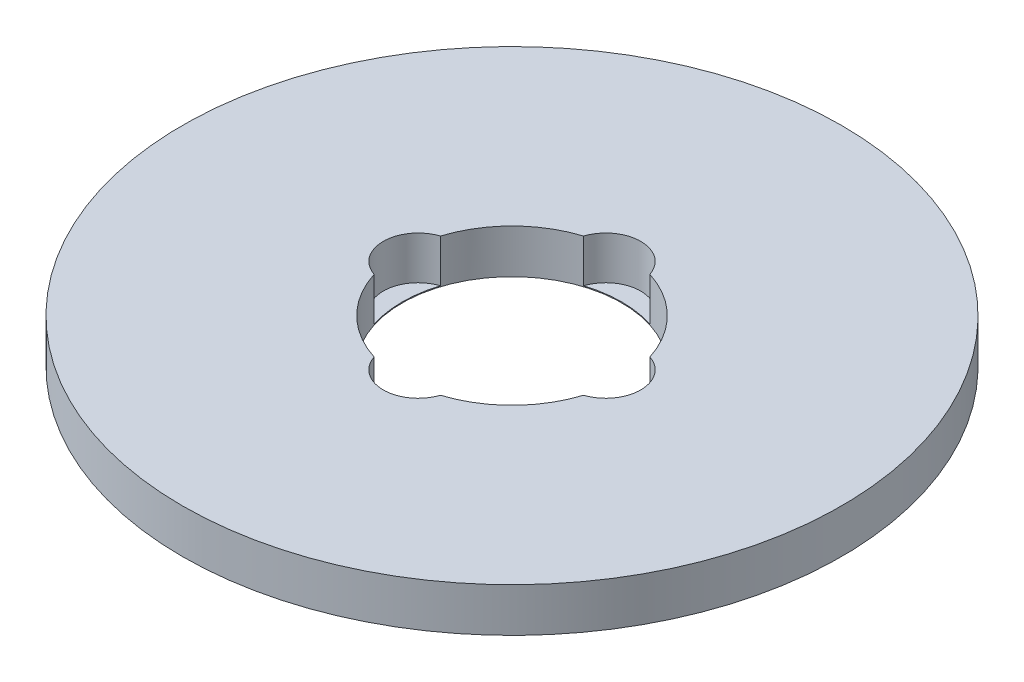
SolidWorks part; units mm, degrees
ref_plane "Front Plane" through (0, 0, 0) normal (0, 0, 1) x (1, 0, 0)
ref_plane "Top Plane" through (0, 0, 0) normal (0, 1, 0) x (1, 0, 0)
ref_plane "Right Plane" through (0, 0, 0) normal (1, 0, 0) x (0, 0, -1)
sketch "Sketch1" plane through (0, 0, 0) normal (0, 1, 0) x (1, 0, 0)
  circle A0 centre (0, 0) radius 30
  dimension "FLANGE_OD" = 60
extrude "Boss-Extrude1" add sketch "Sketch1" along normal blind 4
sketch "Sketch2" plane through (0, 0, 0) normal (0, 1, 0) x (1, 0, 0)
  circle A0 centre (0, 0) radius 10
  dimension "BORE_D" = 20
extrude "Cut-Extrude1" cut sketch "Sketch2" along normal through all
sketch "Sketch3" plane through (0, 4, 0) normal (0, 1, 0) x (1, 0, 0)
  circle A0 centre (0, 0) radius 8.5414 construction
  circle A1 centre (-8.5414, 0) radius 3.1767
  dimension "BOLT_D" = 6.3534
  dimension "BOLT_PCD" = 17.0827
extrude "Cut-Extrude2" cut sketch "Sketch3" against normal blind 3.9222
pattern_circular "CirPattern1" count 4 over 360 about axis through (0, 0, 0) along (0, 1, 0) of "Cut-Extrude2"
